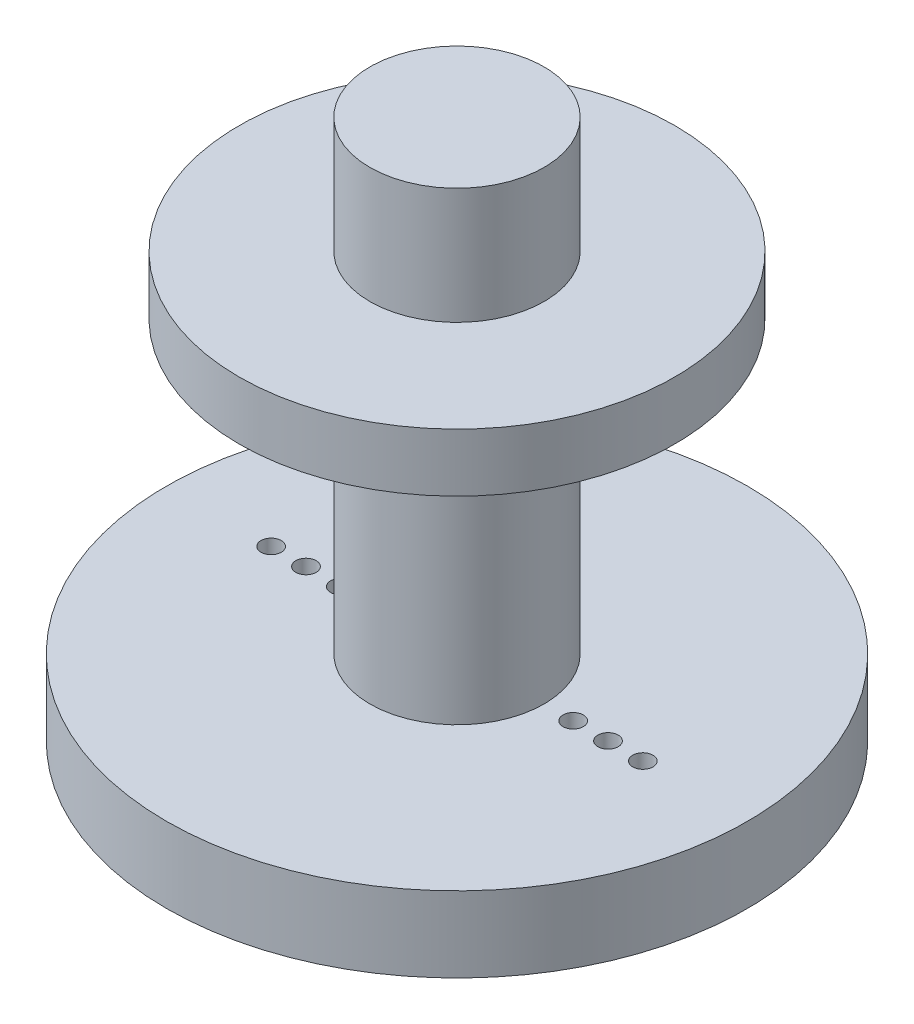
SolidWorks part; units mm, degrees
ref_plane "Front Plane" through (0, 0, 0) normal (0, 0, 1) x (1, 0, 0)
ref_plane "Top Plane" through (0, 0, 0) normal (0, 1, 0) x (1, 0, 0)
ref_plane "Right Plane" through (0, 0, 0) normal (1, 0, 0) x (0, 0, -1)
sketch "Sketch1" plane through (0, 0, 0) normal (0, 1, 0) x (1, 0, 0)
  circle A0 centre (0, 0) radius 25
  dimension "D1" = 50
extrude "Boss-Extrude1" add sketch "Sketch1" along normal blind 6.5 contours A0
sketch "Sketch8" plane through (0, 0, 0) normal (0, -1, 0) x (1, 0, 0)
  line L4 (0, 25) -> (0, -25) construction
  line L5 (-25, 0) -> (25, 0) construction
  circle A4 centre (0, 0) radius 25 construction
  arc A19 (2.8678, 6.2766) -> (8.1035, 4.0243) centre (-3.6427, -16.0687) cw
  arc A20 (8.1035, 4.0243) -> (17.4455, 2.5243) centre (-5.206, -108.7086) cw
  arc A21 (17.4455, 2.5243) -> (21, -0.4757) centre (17.8847, -0.5611) cw
  arc A22 (17.4455, -2.5243) -> (21, -0.4757) centre (18.0512, 0.5327) ccw
  arc A23 (2.8678, -6.2766) -> (8.1035, -4.0243) centre (-3.6427, 16.0687) ccw
  arc A24 (8.1035, -4.0243) -> (17.4455, -2.5243) centre (-5.206, 108.7086) ccw
  arc A25 (2.8678, 6.2766) -> (-2.8678, 6.2766) centre (0, 0) ccw
  arc A26 (-2.8678, -6.2766) -> (2.8678, -6.2766) centre (0, 0) ccw
  arc A27 (-2.8678, 6.2766) -> (-8.1035, 4.0243) centre (3.6427, -16.0687) ccw
  arc A28 (-8.1035, 4.0243) -> (-17.4455, 2.5243) centre (5.206, -108.7086) ccw
  arc A29 (-17.4455, 2.5243) -> (-21, -0.4757) centre (-17.8847, -0.5611) ccw
  arc A30 (-17.4455, -3.4757) -> (-21, -0.4757) centre (-17.8847, -0.3904) cw
  arc A31 (-8.1035, -4.0243) -> (-17.4455, -3.4757) centre (-6.1266, 109.4743) cw
  arc A32 (-2.8678, -6.2766) -> (-8.1035, -4.0243) centre (3.6427, 16.0687) cw
extrude "Horn Hole" cut sketch "Sketch8" against normal blind 2
sketch "Sketch9" plane through (0, 2, 0) normal (0, -1, 0) x (1, 0, 0)
  line L0 (0, 0) -> (7, 0) construction
  line L1 (0, 0) -> (0, -2.0664) construction
  circle A0 centre (7, 0) radius 0.875 construction
  circle A1 centre (10, 0) radius 0.875
  circle A8 centre (13, 0) radius 0.875
  circle A9 centre (16, 0) radius 0.875
  circle A10 centre (-7, 0) radius 0.875 construction
  circle A11 centre (-10, 0) radius 0.875
  circle A12 centre (-13, 0) radius 0.875
  circle A13 centre (-16, 0) radius 0.875
  dimension "D2" = 1.75
  dimension "D1" = 7
  dimension "D3" = 4
extrude "Screw Holes" cut sketch "Sketch9" against normal up to next
sketch "Sketch11" plane through (0, 6.5, 0) normal (0, 1, 0) x (1, 0, 0)
  circle A1 centre (0, 0) radius 7.5
  dimension "D1" = 15
extrude "Boss-Extrude2" add sketch "Sketch11" along normal blind 25
sketch "Sketch12" plane through (0, 31.5, 0) normal (0, 1, 0) x (1, 0, 0)
  circle A0 centre (0, 0) radius 18.75
extrude "Boss-Extrude3" add sketch "Sketch12" along normal blind 5
sketch "Sketch13" plane through (0, 2, 0) normal (0, -1, 0) x (1, 0, 0)
  line L0 (3.4, 0) -> (-3.4, 0)
  arc A0 (3.4, 0) -> (-3.4, 0) centre (0, 0) cw
  point P4 (0, 0)
  dimension "D2" = 3.4
  dimension "D1" = 6.8
revolve "Screw Head Hole" cut sketch "Sketch13" angle 180 about L0 reverse direction yes
extrude "Boss-Extrude4" add sketch "Sketch11<2>" along normal blind 10 from surface starting at face at (0, 36.5, 18.75)
sketch "Sketch11<2>" plane through (0, 6.5, 0) normal (0, 1, 0) x (1, 0, 0) same geometry as "Sketch11"
